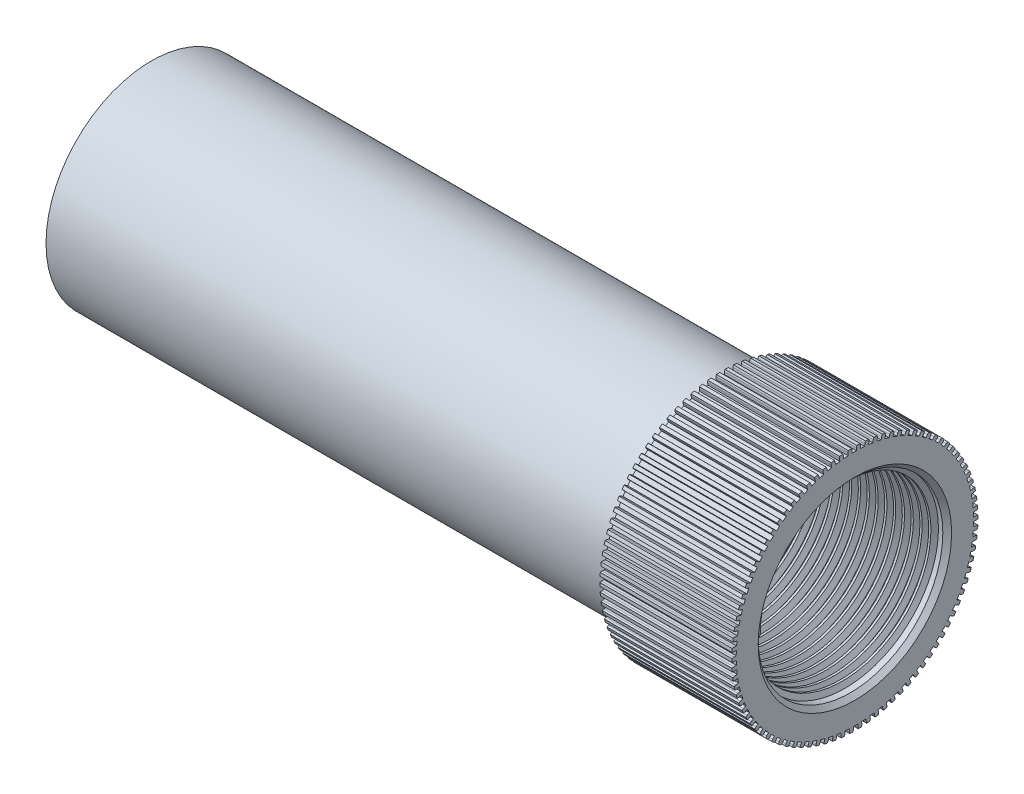
SolidWorks part; units mm, degrees
material "1060 Сплав"
ref_plane "Спереди" through (0, 0, 0) normal (0, 0, 1) x (1, 0, 0)
ref_plane "Сверху" through (0, 0, 0) normal (0, 1, 0) x (1, 0, 0)
ref_plane "Справа" through (0, 0, 0) normal (1, 0, 0) x (0, 0, -1)
sketch "Эскиз1" plane through (0, 0, 0) normal (0, 0, 1) x (1, 0, 0)
  line L0 (39.1314, 14) -> (24.1314, 14)
  line L1 (24.1314, 14) -> (24.1314, 12)
  line L2 (24.1314, 12) -> (-40.8686, 12)
  line L3 (-40.8686, 12) -> (-40.8686, 10.5)
  line L4 (-40.8686, 10.5) -> (-25.8686, 10.5)
  line L5 (-25.8686, 10.5) -> (-25.8686, 8.5)
  line L6 (-25.8686, 8.5) -> (23.1314, 8.5)
  line L7 (23.1314, 8.5) -> (23.1314, 10.5)
  line L8 (23.1314, 10.5) -> (39.1314, 10.5)
  line L9 (39.1314, 10.5) -> (39.1314, 14)
  line L10 (-1.2343, 0) -> (0, 0) construction
  line L11 (0, 0) -> (51.2914, 0) construction
  dimension "D1" = 12
  dimension "D2" = 65
  dimension "D3" = 2
  dimension "D4" = 15
  dimension "D5" = 10.5
  dimension "D6" = 3.5
  dimension "D7" = 8.5
  dimension "D8" = 10.5
  dimension "D9" = 16
  dimension "D10" = 15
revolve "Повернуть1" add sketch "Эскиз1" angle 360 about L11
chamfer "Фаска1" distance 0.5 angle 45 1 edges at (39.1314, 0, 10.5)
thread "Резьба1" pitch 1 method extrude profile "Профиль резьбы2" start angle 0, offset 0, length 15, pitch 1, diameter 21
ref_plane "Плоскость2" through (38.6314, 0, 10.5) normal (0, -1, 0) x (0, 0, 1)
sketch "Профиль резьбы2" plane through (38.6314, 0, 10.5) normal (0, -1, 0) x (0, 0, 1)
  line L0 (0, 0) -> (0, 1) construction
  line L11 (0, 0) -> (0, 0.875)
  line L12 (0, 0.875) -> (-0.5413, 0.5625)
  line L13 (-0.5413, 0.5625) -> (-0.5413, 0.3125)
  line L15 (-0.5413, 0.3125) -> (0, 0)
  line L17 (-0.5413, 0.4375) -> (0, 0.4375) construction
  point P2 (0, 0)
  dimension "Pitch" = 1
  dimension "Profile_Angle" = 60
  dimension "Profile_Land" = 0.25
  dimension "Profile_Height" = 0.5413
thread "Резьба2" pitch 1 method extrude profile "Профиль резьбы3" start angle 0, offset 0, length 15, pitch 1, diameter 21
ref_plane "Плоскость3" through (-40.8686, 0, -10.5) normal (0, -1, 0) x (0, 0, -1)
sketch "Профиль резьбы3" plane through (-40.8686, 0, -10.5) normal (0, -1, 0) x (0, 0, -1)
  line L0 (0, 0) -> (0, 1) construction
  line L11 (0, 0) -> (0, 0.875)
  line L12 (0, 0.875) -> (-0.5413, 0.5625)
  line L13 (-0.5413, 0.5625) -> (-0.5413, 0.3125)
  line L15 (-0.5413, 0.3125) -> (0, 0)
  line L17 (-0.5413, 0.4375) -> (0, 0.4375) construction
  point P2 (0, 0)
  dimension "Pitch" = 1
  dimension "Profile_Angle" = 60
  dimension "Profile_Land" = 0.25
  dimension "Profile_Height" = 0.5413
sketch "Эскиз2" plane through (39.1314, 0, 0) normal (1, 0, 0) x (0, 0, -1)
  line L0 (-0.0776, 1.5379) -> (-0.0776, 20.4101) construction
  line L1 (-0.3776, 14) -> (-0.3276, 13.8)
  line L2 (-0.3276, 13.8) -> (-0.3276, 13.5)
  line L3 (-0.3276, 13.5) -> (0.1724, 13.5)
  line L4 (0.1724, 13.5) -> (0.1724, 13.8)
  line L5 (0.1724, 13.8) -> (0.2224, 14)
  line L6 (0.2224, 14) -> (-0.3776, 14)
  line L7 (0.5999, 13.9922) -> (0.6358, 13.7892)
  line L8 (0.6358, 13.7892) -> (0.6149, 13.49)
  line L9 (0.6149, 13.49) -> (1.1137, 13.4551)
  line L10 (1.1137, 13.4551) -> (1.1346, 13.7544)
  line L11 (1.1346, 13.7544) -> (1.1984, 13.9504)
  line L12 (1.1984, 13.9504) -> (0.5999, 13.9922)
  line L13 (1.5745, 13.9163) -> (1.5961, 13.7113)
  line L14 (1.5961, 13.7113) -> (1.5544, 13.4142)
  line L15 (1.5544, 13.4142) -> (2.0495, 13.3446)
  line L16 (2.0495, 13.3446) -> (2.0913, 13.6417)
  line L17 (2.0913, 13.6417) -> (2.1686, 13.8328)
  line L18 (2.1686, 13.8328) -> (1.5745, 13.9163)
  line L19 (2.5414, 13.7726) -> (2.5487, 13.5666)
  line L20 (2.5487, 13.5666) -> (2.4863, 13.2731)
  line L21 (2.4863, 13.2731) -> (2.9754, 13.1692)
  line L22 (2.9754, 13.1692) -> (3.0378, 13.4626)
  line L23 (3.0378, 13.4626) -> (3.1283, 13.6478)
  line L24 (3.1283, 13.6478) -> (2.5414, 13.7726)
  line L25 (3.4959, 13.5618) -> (3.4888, 13.3557)
  line L26 (3.4888, 13.3557) -> (3.4062, 13.0673)
  line L27 (3.4062, 13.0673) -> (3.8868, 12.9295)
  line L28 (3.8868, 12.9295) -> (3.9695, 13.2179)
  line L29 (3.9695, 13.2179) -> (4.0727, 13.3964)
  line L30 (4.0727, 13.3964) -> (3.4959, 13.5618)
  line L31 (4.4334, 13.2849) -> (4.412, 13.0798)
  line L32 (4.412, 13.0798) -> (4.3094, 12.7979)
  line L33 (4.3094, 12.7979) -> (4.7792, 12.6269)
  line L34 (4.7792, 12.6269) -> (4.8818, 12.9088)
  line L35 (4.8818, 12.9088) -> (4.9972, 13.0796)
  line L36 (4.9972, 13.0796) -> (4.4334, 13.2849)
  line L37 (5.3493, 12.9432) -> (5.3136, 12.7402)
  line L38 (5.3136, 12.7402) -> (5.1916, 12.4661)
  line L39 (5.1916, 12.4661) -> (5.6484, 12.2628)
  line L40 (5.6484, 12.2628) -> (5.7704, 12.5368)
  line L41 (5.7704, 12.5368) -> (5.8974, 12.6992)
  line L42 (5.8974, 12.6992) -> (5.3493, 12.9432)
  line L43 (6.2392, 12.5386) -> (6.1894, 12.3385)
  line L44 (6.1894, 12.3385) -> (6.0486, 12.0736)
  line L45 (6.0486, 12.0736) -> (6.49, 11.8389)
  line L46 (6.49, 11.8389) -> (6.6309, 12.1038)
  line L47 (6.6309, 12.1038) -> (6.7689, 12.2569)
  line L48 (6.7689, 12.2569) -> (6.2392, 12.5386)
  line L49 (7.0986, 12.0728) -> (7.035, 11.8767)
  line L50 (7.035, 11.8767) -> (6.8761, 11.6223)
  line L51 (6.8761, 11.6223) -> (7.3001, 11.3573)
  line L52 (7.3001, 11.3573) -> (7.4591, 11.6117)
  line L53 (7.4591, 11.6117) -> (7.6074, 11.7548)
  line L54 (7.6074, 11.7548) -> (7.0986, 12.0728)
  line L55 (7.9235, 11.5482) -> (7.8464, 11.357)
  line L56 (7.8464, 11.357) -> (7.67, 11.1143)
  line L57 (7.67, 11.1143) -> (8.0745, 10.8204)
  line L58 (8.0745, 10.8204) -> (8.2509, 11.0631)
  line L59 (8.2509, 11.0631) -> (8.4089, 11.1955)
  line L60 (8.4089, 11.1955) -> (7.9235, 11.5482)
  line L61 (8.7097, 10.9674) -> (8.6195, 10.782)
  line L62 (8.6195, 10.782) -> (8.4266, 10.5522)
  line L63 (8.4266, 10.5522) -> (8.8097, 10.2308)
  line L64 (8.8097, 10.2308) -> (9.0025, 10.4606)
  line L65 (9.0025, 10.4606) -> (9.1694, 10.5817)
  line L66 (9.1694, 10.5817) -> (8.7097, 10.9674)
  line L67 (9.4536, 10.3331) -> (9.3506, 10.1545)
  line L68 (9.3506, 10.1545) -> (9.1422, 9.9387)
  line L69 (9.1422, 9.9387) -> (9.5019, 9.5914)
  line L70 (9.5019, 9.5914) -> (9.7103, 9.8072)
  line L71 (9.7103, 9.8072) -> (9.8852, 9.9163)
  line L72 (9.8852, 9.9163) -> (9.4536, 10.3331)
  line L73 (10.1513, 9.6485) -> (10.0362, 9.4775)
  line L74 (10.0362, 9.4775) -> (9.8132, 9.2767)
  line L75 (9.8132, 9.2767) -> (10.1478, 8.9052)
  line L76 (10.1478, 8.9052) -> (10.3707, 9.1059)
  line L77 (10.3707, 9.1059) -> (10.5528, 9.2026)
  line L78 (10.5528, 9.2026) -> (10.1513, 9.6485)
  line L79 (10.7997, 8.9168) -> (10.6728, 8.7543)
  line L80 (10.6728, 8.7543) -> (10.4364, 8.5696)
  line L81 (10.4364, 8.5696) -> (10.7443, 8.1756)
  line L82 (10.7443, 8.1756) -> (10.9807, 8.3603)
  line L83 (10.9807, 8.3603) -> (11.169, 8.444)
  line L84 (11.169, 8.444) -> (10.7997, 8.9168)
  line L85 (11.3954, 8.1418) -> (11.2575, 7.9885)
  line L86 (11.2575, 7.9885) -> (11.0088, 7.8207)
  line L87 (11.0088, 7.8207) -> (11.2884, 7.4062)
  line L88 (11.2884, 7.4062) -> (11.5371, 7.574)
  line L89 (11.5371, 7.574) -> (11.7309, 7.6444)
  line L90 (11.7309, 7.6444) -> (11.3954, 8.1418)
  line L91 (11.9355, 7.327) -> (11.7873, 7.1837)
  line L92 (11.7873, 7.1837) -> (11.5275, 7.0337)
  line L93 (11.5275, 7.0337) -> (11.7775, 6.6007)
  line L94 (11.7775, 6.6007) -> (12.0373, 6.7507)
  line L95 (12.0373, 6.7507) -> (12.2355, 6.8074)
  line L96 (12.2355, 6.8074) -> (11.9355, 7.327)
  line L97 (12.4176, 6.4766) -> (12.2597, 6.344)
  line L98 (12.2597, 6.344) -> (11.9901, 6.2125)
  line L99 (11.9901, 6.2125) -> (12.2093, 5.7631)
  line L100 (12.2093, 5.7631) -> (12.4789, 5.8946)
  line L101 (12.4789, 5.8946) -> (12.6806, 5.9373)
  line L102 (12.6806, 5.9373) -> (12.4176, 6.4766)
  line L103 (12.8391, 5.5946) -> (12.6724, 5.4734)
  line L104 (12.6724, 5.4734) -> (12.3942, 5.361)
  line L105 (12.3942, 5.361) -> (12.5815, 4.8974)
  line L106 (12.5815, 4.8974) -> (12.8597, 5.0098)
  line L107 (12.8597, 5.0098) -> (13.0639, 5.0383)
  line L108 (13.0639, 5.0383) -> (12.8391, 5.5946)
  line L109 (13.1981, 4.6854) -> (13.0233, 4.576)
  line L110 (13.0233, 4.576) -> (12.738, 4.4833)
  line L111 (12.738, 4.4833) -> (12.8925, 4.0078)
  line L112 (12.8925, 4.0078) -> (13.1778, 4.1005)
  line L113 (13.1778, 4.1005) -> (13.3835, 4.1148)
  line L114 (13.3835, 4.1148) -> (13.1981, 4.6854)
  line L115 (13.4928, 3.7533) -> (13.3108, 3.6564)
  line L116 (13.3108, 3.6564) -> (13.0197, 3.5839)
  line L117 (13.0197, 3.5839) -> (13.1407, 3.0987)
  line L118 (13.1407, 3.0987) -> (13.4318, 3.1713)
  line L119 (13.4318, 3.1713) -> (13.6379, 3.1712)
  line L120 (13.6379, 3.1712) -> (13.4928, 3.7533)
  line L121 (13.7217, 2.803) -> (13.5335, 2.719)
  line L122 (13.5335, 2.719) -> (13.238, 2.6669)
  line L123 (13.238, 2.6669) -> (13.3248, 2.1745)
  line L124 (13.3248, 2.1745) -> (13.6203, 2.2266)
  line L125 (13.6203, 2.2266) -> (13.8259, 2.2121)
  line L126 (13.8259, 2.2121) -> (13.7217, 2.803)
  line L127 (13.8838, 1.839) -> (13.6902, 1.7683)
  line L128 (13.6902, 1.7683) -> (13.3918, 1.737)
  line L129 (13.3918, 1.737) -> (13.4441, 1.2397)
  line L130 (13.4441, 1.2397) -> (13.7424, 1.2711)
  line L131 (13.7424, 1.2711) -> (13.9465, 1.2423)
  line L132 (13.9465, 1.2423) -> (13.8838, 1.839)
  line L133 (13.9783, 0.866) -> (13.7802, 0.8091)
  line L134 (13.7802, 0.8091) -> (13.4803, 0.7986)
  line L135 (13.4803, 0.7986) -> (13.4978, 0.2989)
  line L136 (13.4978, 0.2989) -> (13.7976, 0.3094)
  line L137 (13.7976, 0.3094) -> (13.9992, 0.2664)
  line L138 (13.9992, 0.2664) -> (13.9783, 0.866)
  line L139 (14.0047, -0.1112) -> (13.803, -0.1542)
  line L140 (13.803, -0.1542) -> (13.5032, -0.1437)
  line L141 (13.5032, -0.1437) -> (13.4858, -0.6434)
  line L142 (13.4858, -0.6434) -> (13.7856, -0.6539)
  line L143 (13.7856, -0.6539) -> (13.9837, -0.7108)
  line L144 (13.9837, -0.7108) -> (14.0047, -0.1112)
  line L145 (13.9628, -1.0878) -> (13.7587, -1.1166)
  line L146 (13.7587, -1.1166) -> (13.4603, -1.0853)
  line L147 (13.4603, -1.0853) -> (13.408, -1.5825)
  line L148 (13.408, -1.5825) -> (13.7064, -1.6139)
  line L149 (13.7064, -1.6139) -> (13.9001, -1.6845)
  line L150 (13.9001, -1.6845) -> (13.9628, -1.0878)
  line L151 (13.8529, -2.0592) -> (13.6472, -2.0737)
  line L152 (13.6472, -2.0737) -> (13.3518, -2.0216)
  line L153 (13.3518, -2.0216) -> (13.265, -2.514)
  line L154 (13.265, -2.514) -> (13.5604, -2.5661)
  line L155 (13.5604, -2.5661) -> (13.7487, -2.6501)
  line L156 (13.7487, -2.6501) -> (13.8529, -2.0592)
  line L157 (13.6755, -3.0205) -> (13.4693, -3.0206)
  line L158 (13.4693, -3.0206) -> (13.1783, -2.948)
  line L159 (13.1783, -2.948) -> (13.0573, -3.4332)
  line L160 (13.0573, -3.4332) -> (13.3484, -3.5058)
  line L161 (13.3484, -3.5058) -> (13.5303, -3.6027)
  line L162 (13.5303, -3.6027) -> (13.6755, -3.0205)
  line L163 (13.4315, -3.9671) -> (13.2258, -3.9528)
  line L164 (13.2258, -3.9528) -> (12.9405, -3.8601)
  line L165 (12.9405, -3.8601) -> (12.786, -4.3357)
  line L166 (12.786, -4.3357) -> (13.0713, -4.4284)
  line L167 (13.0713, -4.4284) -> (13.2461, -4.5377)
  line L168 (13.2461, -4.5377) -> (13.4315, -3.9671)
  line L169 (13.122, -4.8943) -> (12.9179, -4.8658)
  line L170 (12.9179, -4.8658) -> (12.6397, -4.7534)
  line L171 (12.6397, -4.7534) -> (12.4524, -5.217)
  line L172 (12.4524, -5.217) -> (12.7306, -5.3294)
  line L173 (12.7306, -5.3294) -> (12.8973, -5.4507)
  line L174 (12.8973, -5.4507) -> (13.122, -4.8943)
  line L175 (12.7487, -5.7978) -> (12.547, -5.755)
  line L176 (12.547, -5.755) -> (12.2773, -5.6235)
  line L177 (12.2773, -5.6235) -> (12.0582, -6.0729)
  line L178 (12.0582, -6.0729) -> (12.3278, -6.2044)
  line L179 (12.3278, -6.2044) -> (12.4856, -6.337)
  line L180 (12.4856, -6.337) -> (12.7487, -5.7978)
  line L181 (12.3132, -6.673) -> (12.115, -6.6163)
  line L182 (12.115, -6.6163) -> (11.8552, -6.4663)
  line L183 (11.8552, -6.4663) -> (11.6052, -6.8993)
  line L184 (11.6052, -6.8993) -> (11.865, -7.0493)
  line L185 (11.865, -7.0493) -> (12.0132, -7.1926)
  line L186 (12.0132, -7.1926) -> (12.3132, -6.673)
  line L187 (11.8177, -7.5156) -> (11.6239, -7.4452)
  line L188 (11.6239, -7.4452) -> (11.3752, -7.2775)
  line L189 (11.3752, -7.2775) -> (11.0956, -7.692)
  line L190 (11.0956, -7.692) -> (11.3443, -7.8598)
  line L191 (11.3443, -7.8598) -> (11.4822, -8.013)
  line L192 (11.4822, -8.013) -> (11.8177, -7.5156)
  line L193 (11.2647, -8.3217) -> (11.0763, -8.2379)
  line L194 (11.0763, -8.2379) -> (10.8399, -8.0532)
  line L195 (10.8399, -8.0532) -> (10.532, -8.4472)
  line L196 (10.532, -8.4472) -> (10.7684, -8.6319)
  line L197 (10.7684, -8.6319) -> (10.8953, -8.7945)
  line L198 (10.8953, -8.7945) -> (11.2647, -8.3217)
  line L199 (10.6567, -9.0872) -> (10.4746, -8.9905)
  line L200 (10.4746, -8.9905) -> (10.2517, -8.7898)
  line L201 (10.2517, -8.7898) -> (9.9171, -9.1613)
  line L202 (9.9171, -9.1613) -> (10.1401, -9.3621)
  line L203 (10.1401, -9.3621) -> (10.2552, -9.5331)
  line L204 (10.2552, -9.5331) -> (10.6567, -9.0872)
  line L205 (9.9969, -9.8084) -> (9.822, -9.6993)
  line L206 (9.822, -9.6993) -> (9.6136, -9.4835)
  line L207 (9.6136, -9.4835) -> (9.2539, -9.8308)
  line L208 (9.2539, -9.8308) -> (9.4623, -10.0466)
  line L209 (9.4623, -10.0466) -> (9.5653, -10.2252)
  line L210 (9.5653, -10.2252) -> (9.9969, -9.8084)
  line L211 (9.2883, -10.4819) -> (9.1215, -10.3608)
  line L212 (9.1215, -10.3608) -> (8.9286, -10.131)
  line L213 (8.9286, -10.131) -> (8.5456, -10.4524)
  line L214 (8.5456, -10.4524) -> (8.7384, -10.6822)
  line L215 (8.7384, -10.6822) -> (8.8287, -10.8676)
  line L216 (8.8287, -10.8676) -> (9.2883, -10.4819)
  line L217 (8.5345, -11.1043) -> (8.3765, -10.9719)
  line L218 (8.3765, -10.9719) -> (8.2002, -10.7291)
  line L219 (8.2002, -10.7291) -> (7.7957, -11.023)
  line L220 (7.7957, -11.023) -> (7.972, -11.2657)
  line L221 (7.972, -11.2657) -> (8.0491, -11.4569)
  line L222 (8.0491, -11.4569) -> (8.5345, -11.1043)
  line L223 (7.7391, -11.6726) -> (7.5907, -11.5294)
  line L224 (7.5907, -11.5294) -> (7.4318, -11.275)
  line L225 (7.4318, -11.275) -> (7.0077, -11.54)
  line L226 (7.0077, -11.54) -> (7.1667, -11.7944)
  line L227 (7.1667, -11.7944) -> (7.2303, -11.9905)
  line L228 (7.2303, -11.9905) -> (7.7391, -11.6726)
  line L229 (6.906, -12.184) -> (6.768, -12.0309)
  line L230 (6.768, -12.0309) -> (6.6272, -11.766)
  line L231 (6.6272, -11.766) -> (6.1857, -12.0007)
  line L232 (6.1857, -12.0007) -> (6.3265, -12.2656)
  line L233 (6.3265, -12.2656) -> (6.3763, -12.4657)
  line L234 (6.3763, -12.4657) -> (6.906, -12.184)
  line L235 (6.0393, -12.636) -> (5.9123, -12.4737)
  line L236 (5.9123, -12.4737) -> (5.7903, -12.1996)
  line L237 (5.7903, -12.1996) -> (5.3335, -12.403)
  line L238 (5.3335, -12.403) -> (5.4555, -12.677)
  line L239 (5.4555, -12.677) -> (5.4912, -12.8801)
  line L240 (5.4912, -12.8801) -> (6.0393, -12.636)
  line L241 (5.1431, -13.0265) -> (5.0278, -12.8557)
  line L242 (5.0278, -12.8557) -> (4.9252, -12.5738)
  line L243 (4.9252, -12.5738) -> (4.4553, -12.7448)
  line L244 (4.4553, -12.7448) -> (4.5579, -13.0267)
  line L245 (4.5579, -13.0267) -> (4.5793, -13.2317)
  line L246 (4.5793, -13.2317) -> (5.1431, -13.0265)
  line L247 (4.2219, -13.3536) -> (4.1187, -13.1751)
  line L248 (4.1187, -13.1751) -> (4.0361, -12.8867)
  line L249 (4.0361, -12.8867) -> (3.5554, -13.0245)
  line L250 (3.5554, -13.0245) -> (3.6381, -13.3129)
  line L251 (3.6381, -13.3129) -> (3.6452, -13.519)
  line L252 (3.6452, -13.519) -> (4.2219, -13.3536)
  line L253 (3.2802, -13.6156) -> (3.1897, -13.4303)
  line L254 (3.1897, -13.4303) -> (3.1273, -13.1369)
  line L255 (3.1273, -13.1369) -> (2.6382, -13.2408)
  line L256 (2.6382, -13.2408) -> (2.7006, -13.5343)
  line L257 (2.7006, -13.5343) -> (2.6933, -13.7403)
  line L258 (2.6933, -13.7403) -> (3.2802, -13.6156)
  line L259 (2.3224, -13.8112) -> (2.245, -13.6201)
  line L260 (2.245, -13.6201) -> (2.2033, -13.323)
  line L261 (2.2033, -13.323) -> (1.7082, -13.3926)
  line L262 (1.7082, -13.3926) -> (1.7499, -13.6897)
  line L263 (1.7499, -13.6897) -> (1.7282, -13.8947)
  line L264 (1.7282, -13.8947) -> (2.3224, -13.8112)
  line L265 (1.3533, -13.9396) -> (1.2895, -13.7435)
  line L266 (1.2895, -13.7435) -> (1.2686, -13.4443)
  line L267 (1.2686, -13.4443) -> (0.7698, -13.4791)
  line L268 (0.7698, -13.4791) -> (0.7907, -13.7784)
  line L269 (0.7907, -13.7784) -> (0.7548, -13.9814)
  line L270 (0.7548, -13.9814) -> (1.3533, -13.9396)
  line L271 (0.3776, -14) -> (0.3276, -13.8)
  line L272 (0.3276, -13.8) -> (0.3276, -13.5)
  line L273 (0.3276, -13.5) -> (-0.1724, -13.5)
  line L274 (-0.1724, -13.5) -> (-0.1724, -13.8)
  line L275 (-0.1724, -13.8) -> (-0.2224, -14)
  line L276 (-0.2224, -14) -> (0.3776, -14)
  line L277 (-0.5999, -13.9922) -> (-0.6358, -13.7892)
  line L278 (-0.6358, -13.7892) -> (-0.6149, -13.49)
  line L279 (-0.6149, -13.49) -> (-1.1137, -13.4551)
  line L280 (-1.1137, -13.4551) -> (-1.1346, -13.7544)
  line L281 (-1.1346, -13.7544) -> (-1.1984, -13.9504)
  line L282 (-1.1984, -13.9504) -> (-0.5999, -13.9922)
  line L283 (-1.5745, -13.9163) -> (-1.5961, -13.7113)
  line L284 (-1.5961, -13.7113) -> (-1.5544, -13.4142)
  line L285 (-1.5544, -13.4142) -> (-2.0495, -13.3446)
  line L286 (-2.0495, -13.3446) -> (-2.0913, -13.6417)
  line L287 (-2.0913, -13.6417) -> (-2.1686, -13.8328)
  line L288 (-2.1686, -13.8328) -> (-1.5745, -13.9163)
  line L289 (-2.5414, -13.7726) -> (-2.5487, -13.5666)
  line L290 (-2.5487, -13.5666) -> (-2.4863, -13.2731)
  line L291 (-2.4863, -13.2731) -> (-2.9754, -13.1692)
  line L292 (-2.9754, -13.1692) -> (-3.0378, -13.4626)
  line L293 (-3.0378, -13.4626) -> (-3.1283, -13.6478)
  line L294 (-3.1283, -13.6478) -> (-2.5414, -13.7726)
  line L295 (-3.4959, -13.5618) -> (-3.4888, -13.3557)
  line L296 (-3.4888, -13.3557) -> (-3.4062, -13.0673)
  line L297 (-3.4062, -13.0673) -> (-3.8868, -12.9295)
  line L298 (-3.8868, -12.9295) -> (-3.9695, -13.2179)
  line L299 (-3.9695, -13.2179) -> (-4.0727, -13.3964)
  line L300 (-4.0727, -13.3964) -> (-3.4959, -13.5618)
  line L301 (-4.4334, -13.2849) -> (-4.412, -13.0798)
  line L302 (-4.412, -13.0798) -> (-4.3094, -12.7979)
  line L303 (-4.3094, -12.7979) -> (-4.7792, -12.6269)
  line L304 (-4.7792, -12.6269) -> (-4.8818, -12.9088)
  line L305 (-4.8818, -12.9088) -> (-4.9972, -13.0796)
  line L306 (-4.9972, -13.0796) -> (-4.4334, -13.2849)
  line L307 (-5.3493, -12.9432) -> (-5.3136, -12.7402)
  line L308 (-5.3136, -12.7402) -> (-5.1916, -12.4661)
  line L309 (-5.1916, -12.4661) -> (-5.6484, -12.2628)
  line L310 (-5.6484, -12.2628) -> (-5.7704, -12.5368)
  line L311 (-5.7704, -12.5368) -> (-5.8974, -12.6992)
  line L312 (-5.8974, -12.6992) -> (-5.3493, -12.9432)
  line L313 (-6.2392, -12.5386) -> (-6.1894, -12.3385)
  line L314 (-6.1894, -12.3385) -> (-6.0486, -12.0736)
  line L315 (-6.0486, -12.0736) -> (-6.49, -11.8389)
  line L316 (-6.49, -11.8389) -> (-6.6309, -12.1038)
  line L317 (-6.6309, -12.1038) -> (-6.7689, -12.2569)
  line L318 (-6.7689, -12.2569) -> (-6.2392, -12.5386)
  line L319 (-7.0986, -12.0728) -> (-7.035, -11.8767)
  line L320 (-7.035, -11.8767) -> (-6.8761, -11.6223)
  line L321 (-6.8761, -11.6223) -> (-7.3001, -11.3573)
  line L322 (-7.3001, -11.3573) -> (-7.4591, -11.6117)
  line L323 (-7.4591, -11.6117) -> (-7.6074, -11.7548)
  line L324 (-7.6074, -11.7548) -> (-7.0986, -12.0728)
  line L325 (-7.9235, -11.5482) -> (-7.8464, -11.357)
  line L326 (-7.8464, -11.357) -> (-7.67, -11.1143)
  line L327 (-7.67, -11.1143) -> (-8.0745, -10.8204)
  line L328 (-8.0745, -10.8204) -> (-8.2509, -11.0631)
  line L329 (-8.2509, -11.0631) -> (-8.4089, -11.1955)
  line L330 (-8.4089, -11.1955) -> (-7.9235, -11.5482)
  line L331 (-8.7097, -10.9674) -> (-8.6195, -10.782)
  line L332 (-8.6195, -10.782) -> (-8.4266, -10.5522)
  line L333 (-8.4266, -10.5522) -> (-8.8097, -10.2308)
  line L334 (-8.8097, -10.2308) -> (-9.0025, -10.4606)
  line L335 (-9.0025, -10.4606) -> (-9.1694, -10.5817)
  line L336 (-9.1694, -10.5817) -> (-8.7097, -10.9674)
  line L337 (-9.4536, -10.3331) -> (-9.3506, -10.1545)
  line L338 (-9.3506, -10.1545) -> (-9.1422, -9.9387)
  line L339 (-9.1422, -9.9387) -> (-9.5019, -9.5914)
  line L340 (-9.5019, -9.5914) -> (-9.7103, -9.8072)
  line L341 (-9.7103, -9.8072) -> (-9.8852, -9.9163)
  line L342 (-9.8852, -9.9163) -> (-9.4536, -10.3331)
  line L343 (-10.1513, -9.6485) -> (-10.0362, -9.4775)
  line L344 (-10.0362, -9.4775) -> (-9.8132, -9.2767)
  line L345 (-9.8132, -9.2767) -> (-10.1478, -8.9052)
  line L346 (-10.1478, -8.9052) -> (-10.3707, -9.1059)
  line L347 (-10.3707, -9.1059) -> (-10.5528, -9.2026)
  line L348 (-10.5528, -9.2026) -> (-10.1513, -9.6485)
  line L349 (-10.7997, -8.9168) -> (-10.6728, -8.7543)
  line L350 (-10.6728, -8.7543) -> (-10.4364, -8.5696)
  line L351 (-10.4364, -8.5696) -> (-10.7443, -8.1756)
  line L352 (-10.7443, -8.1756) -> (-10.9807, -8.3603)
  line L353 (-10.9807, -8.3603) -> (-11.169, -8.444)
  line L354 (-11.169, -8.444) -> (-10.7997, -8.9168)
  line L355 (-11.3954, -8.1418) -> (-11.2575, -7.9885)
  line L356 (-11.2575, -7.9885) -> (-11.0088, -7.8207)
  line L357 (-11.0088, -7.8207) -> (-11.2884, -7.4062)
  line L358 (-11.2884, -7.4062) -> (-11.5371, -7.574)
  line L359 (-11.5371, -7.574) -> (-11.7309, -7.6444)
  line L360 (-11.7309, -7.6444) -> (-11.3954, -8.1418)
  line L361 (-11.9355, -7.327) -> (-11.7873, -7.1837)
  line L362 (-11.7873, -7.1837) -> (-11.5275, -7.0337)
  line L363 (-11.5275, -7.0337) -> (-11.7775, -6.6007)
  line L364 (-11.7775, -6.6007) -> (-12.0373, -6.7507)
  line L365 (-12.0373, -6.7507) -> (-12.2355, -6.8074)
  line L366 (-12.2355, -6.8074) -> (-11.9355, -7.327)
  line L367 (-12.4176, -6.4766) -> (-12.2597, -6.344)
  line L368 (-12.2597, -6.344) -> (-11.9901, -6.2125)
  line L369 (-11.9901, -6.2125) -> (-12.2093, -5.7631)
  line L370 (-12.2093, -5.7631) -> (-12.4789, -5.8946)
  line L371 (-12.4789, -5.8946) -> (-12.6806, -5.9373)
  line L372 (-12.6806, -5.9373) -> (-12.4176, -6.4766)
  line L373 (-12.8391, -5.5946) -> (-12.6724, -5.4734)
  line L374 (-12.6724, -5.4734) -> (-12.3942, -5.361)
  line L375 (-12.3942, -5.361) -> (-12.5815, -4.8974)
  line L376 (-12.5815, -4.8974) -> (-12.8597, -5.0098)
  line L377 (-12.8597, -5.0098) -> (-13.0639, -5.0383)
  line L378 (-13.0639, -5.0383) -> (-12.8391, -5.5946)
  line L379 (-13.1981, -4.6854) -> (-13.0233, -4.576)
  line L380 (-13.0233, -4.576) -> (-12.738, -4.4833)
  line L381 (-12.738, -4.4833) -> (-12.8925, -4.0078)
  line L382 (-12.8925, -4.0078) -> (-13.1778, -4.1005)
  line L383 (-13.1778, -4.1005) -> (-13.3835, -4.1148)
  line L384 (-13.3835, -4.1148) -> (-13.1981, -4.6854)
  line L385 (-13.4928, -3.7533) -> (-13.3108, -3.6564)
  line L386 (-13.3108, -3.6564) -> (-13.0197, -3.5839)
  line L387 (-13.0197, -3.5839) -> (-13.1407, -3.0987)
  line L388 (-13.1407, -3.0987) -> (-13.4318, -3.1713)
  line L389 (-13.4318, -3.1713) -> (-13.6379, -3.1712)
  line L390 (-13.6379, -3.1712) -> (-13.4928, -3.7533)
  line L391 (-13.7217, -2.803) -> (-13.5335, -2.719)
  line L392 (-13.5335, -2.719) -> (-13.238, -2.6669)
  line L393 (-13.238, -2.6669) -> (-13.3248, -2.1745)
  line L394 (-13.3248, -2.1745) -> (-13.6203, -2.2266)
  line L395 (-13.6203, -2.2266) -> (-13.8259, -2.2121)
  line L396 (-13.8259, -2.2121) -> (-13.7217, -2.803)
  line L397 (-13.8838, -1.839) -> (-13.6902, -1.7683)
  line L398 (-13.6902, -1.7683) -> (-13.3918, -1.737)
  line L399 (-13.3918, -1.737) -> (-13.4441, -1.2397)
  line L400 (-13.4441, -1.2397) -> (-13.7424, -1.2711)
  line L401 (-13.7424, -1.2711) -> (-13.9465, -1.2423)
  line L402 (-13.9465, -1.2423) -> (-13.8838, -1.839)
  line L403 (-13.9783, -0.866) -> (-13.7802, -0.8091)
  line L404 (-13.7802, -0.8091) -> (-13.4803, -0.7986)
  line L405 (-13.4803, -0.7986) -> (-13.4978, -0.2989)
  line L406 (-13.4978, -0.2989) -> (-13.7976, -0.3094)
  line L407 (-13.7976, -0.3094) -> (-13.9992, -0.2664)
  line L408 (-13.9992, -0.2664) -> (-13.9783, -0.866)
  line L409 (-14.0047, 0.1112) -> (-13.803, 0.1542)
  line L410 (-13.803, 0.1542) -> (-13.5032, 0.1437)
  line L411 (-13.5032, 0.1437) -> (-13.4858, 0.6434)
  line L412 (-13.4858, 0.6434) -> (-13.7856, 0.6539)
  line L413 (-13.7856, 0.6539) -> (-13.9837, 0.7108)
  line L414 (-13.9837, 0.7108) -> (-14.0047, 0.1112)
  line L415 (-13.9628, 1.0878) -> (-13.7587, 1.1166)
  line L416 (-13.7587, 1.1166) -> (-13.4603, 1.0853)
  line L417 (-13.4603, 1.0853) -> (-13.408, 1.5825)
  line L418 (-13.408, 1.5825) -> (-13.7064, 1.6139)
  line L419 (-13.7064, 1.6139) -> (-13.9001, 1.6845)
  line L420 (-13.9001, 1.6845) -> (-13.9628, 1.0878)
  line L421 (-13.8529, 2.0592) -> (-13.6472, 2.0737)
  line L422 (-13.6472, 2.0737) -> (-13.3518, 2.0216)
  line L423 (-13.3518, 2.0216) -> (-13.265, 2.514)
  line L424 (-13.265, 2.514) -> (-13.5604, 2.5661)
  line L425 (-13.5604, 2.5661) -> (-13.7487, 2.6501)
  line L426 (-13.7487, 2.6501) -> (-13.8529, 2.0592)
  line L427 (-13.6755, 3.0205) -> (-13.4693, 3.0206)
  line L428 (-13.4693, 3.0206) -> (-13.1783, 2.948)
  line L429 (-13.1783, 2.948) -> (-13.0573, 3.4332)
  line L430 (-13.0573, 3.4332) -> (-13.3484, 3.5058)
  line L431 (-13.3484, 3.5058) -> (-13.5303, 3.6027)
  line L432 (-13.5303, 3.6027) -> (-13.6755, 3.0205)
  line L433 (-13.4315, 3.9671) -> (-13.2258, 3.9528)
  line L434 (-13.2258, 3.9528) -> (-12.9405, 3.8601)
  line L435 (-12.9405, 3.8601) -> (-12.786, 4.3357)
  line L436 (-12.786, 4.3357) -> (-13.0713, 4.4284)
  line L437 (-13.0713, 4.4284) -> (-13.2461, 4.5377)
  line L438 (-13.2461, 4.5377) -> (-13.4315, 3.9671)
  line L439 (-13.122, 4.8943) -> (-12.9179, 4.8658)
  line L440 (-12.9179, 4.8658) -> (-12.6397, 4.7534)
  line L441 (-12.6397, 4.7534) -> (-12.4524, 5.217)
  line L442 (-12.4524, 5.217) -> (-12.7306, 5.3294)
  line L443 (-12.7306, 5.3294) -> (-12.8973, 5.4507)
  line L444 (-12.8973, 5.4507) -> (-13.122, 4.8943)
  line L445 (-12.7487, 5.7978) -> (-12.547, 5.755)
  line L446 (-12.547, 5.755) -> (-12.2773, 5.6235)
  line L447 (-12.2773, 5.6235) -> (-12.0582, 6.0729)
  line L448 (-12.0582, 6.0729) -> (-12.3278, 6.2044)
  line L449 (-12.3278, 6.2044) -> (-12.4856, 6.337)
  line L450 (-12.4856, 6.337) -> (-12.7487, 5.7978)
  line L451 (-12.3132, 6.673) -> (-12.115, 6.6163)
  line L452 (-12.115, 6.6163) -> (-11.8552, 6.4663)
  line L453 (-11.8552, 6.4663) -> (-11.6052, 6.8993)
  line L454 (-11.6052, 6.8993) -> (-11.865, 7.0493)
  line L455 (-11.865, 7.0493) -> (-12.0132, 7.1926)
  line L456 (-12.0132, 7.1926) -> (-12.3132, 6.673)
  line L457 (-11.8177, 7.5156) -> (-11.6239, 7.4452)
  line L458 (-11.6239, 7.4452) -> (-11.3752, 7.2775)
  line L459 (-11.3752, 7.2775) -> (-11.0956, 7.692)
  line L460 (-11.0956, 7.692) -> (-11.3443, 7.8598)
  line L461 (-11.3443, 7.8598) -> (-11.4822, 8.013)
  line L462 (-11.4822, 8.013) -> (-11.8177, 7.5156)
  line L463 (-11.2647, 8.3217) -> (-11.0763, 8.2379)
  line L464 (-11.0763, 8.2379) -> (-10.8399, 8.0532)
  line L465 (-10.8399, 8.0532) -> (-10.532, 8.4472)
  line L466 (-10.532, 8.4472) -> (-10.7684, 8.6319)
  line L467 (-10.7684, 8.6319) -> (-10.8953, 8.7945)
  line L468 (-10.8953, 8.7945) -> (-11.2647, 8.3217)
  line L469 (-10.6567, 9.0872) -> (-10.4746, 8.9905)
  line L470 (-10.4746, 8.9905) -> (-10.2517, 8.7898)
  line L471 (-10.2517, 8.7898) -> (-9.9171, 9.1613)
  line L472 (-9.9171, 9.1613) -> (-10.1401, 9.3621)
  line L473 (-10.1401, 9.3621) -> (-10.2552, 9.5331)
  line L474 (-10.2552, 9.5331) -> (-10.6567, 9.0872)
  line L475 (-9.9969, 9.8084) -> (-9.822, 9.6993)
  line L476 (-9.822, 9.6993) -> (-9.6136, 9.4835)
  line L477 (-9.6136, 9.4835) -> (-9.2539, 9.8308)
  line L478 (-9.2539, 9.8308) -> (-9.4623, 10.0466)
  line L479 (-9.4623, 10.0466) -> (-9.5653, 10.2252)
  line L480 (-9.5653, 10.2252) -> (-9.9969, 9.8084)
  line L481 (-9.2883, 10.4819) -> (-9.1215, 10.3608)
  line L482 (-9.1215, 10.3608) -> (-8.9286, 10.131)
  line L483 (-8.9286, 10.131) -> (-8.5456, 10.4524)
  line L484 (-8.5456, 10.4524) -> (-8.7384, 10.6822)
  line L485 (-8.7384, 10.6822) -> (-8.8287, 10.8676)
  line L486 (-8.8287, 10.8676) -> (-9.2883, 10.4819)
  line L487 (-8.5345, 11.1043) -> (-8.3765, 10.9719)
  line L488 (-8.3765, 10.9719) -> (-8.2002, 10.7291)
  line L489 (-8.2002, 10.7291) -> (-7.7957, 11.023)
  line L490 (-7.7957, 11.023) -> (-7.972, 11.2657)
  line L491 (-7.972, 11.2657) -> (-8.0491, 11.4569)
  line L492 (-8.0491, 11.4569) -> (-8.5345, 11.1043)
  line L493 (-7.7391, 11.6726) -> (-7.5907, 11.5294)
  line L494 (-7.5907, 11.5294) -> (-7.4318, 11.275)
  line L495 (-7.4318, 11.275) -> (-7.0077, 11.54)
  line L496 (-7.0077, 11.54) -> (-7.1667, 11.7944)
  line L497 (-7.1667, 11.7944) -> (-7.2303, 11.9905)
  line L498 (-7.2303, 11.9905) -> (-7.7391, 11.6726)
  line L499 (-6.906, 12.184) -> (-6.768, 12.0309)
  line L500 (-6.768, 12.0309) -> (-6.6272, 11.766)
  line L501 (-6.6272, 11.766) -> (-6.1857, 12.0007)
  line L502 (-6.1857, 12.0007) -> (-6.3265, 12.2656)
  line L503 (-6.3265, 12.2656) -> (-6.3763, 12.4657)
  line L504 (-6.3763, 12.4657) -> (-6.906, 12.184)
  line L505 (-6.0393, 12.636) -> (-5.9123, 12.4737)
  line L506 (-5.9123, 12.4737) -> (-5.7903, 12.1996)
  line L507 (-5.7903, 12.1996) -> (-5.3335, 12.403)
  line L508 (-5.3335, 12.403) -> (-5.4555, 12.677)
  line L509 (-5.4555, 12.677) -> (-5.4912, 12.8801)
  line L510 (-5.4912, 12.8801) -> (-6.0393, 12.636)
  line L511 (-5.1431, 13.0265) -> (-5.0278, 12.8557)
  line L512 (-5.0278, 12.8557) -> (-4.9252, 12.5738)
  line L513 (-4.9252, 12.5738) -> (-4.4553, 12.7448)
  line L514 (-4.4553, 12.7448) -> (-4.5579, 13.0267)
  line L515 (-4.5579, 13.0267) -> (-4.5793, 13.2317)
  line L516 (-4.5793, 13.2317) -> (-5.1431, 13.0265)
  line L517 (-4.2219, 13.3536) -> (-4.1187, 13.1751)
  line L518 (-4.1187, 13.1751) -> (-4.0361, 12.8867)
  line L519 (-4.0361, 12.8867) -> (-3.5554, 13.0245)
  line L520 (-3.5554, 13.0245) -> (-3.6381, 13.3129)
  line L521 (-3.6381, 13.3129) -> (-3.6452, 13.519)
  line L522 (-3.6452, 13.519) -> (-4.2219, 13.3536)
  line L523 (-3.2802, 13.6156) -> (-3.1897, 13.4303)
  line L524 (-3.1897, 13.4303) -> (-3.1273, 13.1369)
  line L525 (-3.1273, 13.1369) -> (-2.6382, 13.2408)
  line L526 (-2.6382, 13.2408) -> (-2.7006, 13.5343)
  line L527 (-2.7006, 13.5343) -> (-2.6933, 13.7403)
  line L528 (-2.6933, 13.7403) -> (-3.2802, 13.6156)
  line L529 (-2.3224, 13.8112) -> (-2.245, 13.6201)
  line L530 (-2.245, 13.6201) -> (-2.2033, 13.323)
  line L531 (-2.2033, 13.323) -> (-1.7082, 13.3926)
  line L532 (-1.7082, 13.3926) -> (-1.7499, 13.6897)
  line L533 (-1.7499, 13.6897) -> (-1.7282, 13.8947)
  line L534 (-1.7282, 13.8947) -> (-2.3224, 13.8112)
  line L535 (-1.3533, 13.9396) -> (-1.2895, 13.7435)
  line L536 (-1.2895, 13.7435) -> (-1.2686, 13.4443)
  line L537 (-1.2686, 13.4443) -> (-0.7698, 13.4791)
  line L538 (-0.7698, 13.4791) -> (-0.7907, 13.7784)
  line L539 (-0.7907, 13.7784) -> (-0.7548, 13.9814)
  line L540 (-0.7548, 13.9814) -> (-1.3533, 13.9396)
  circle A0 centre (0, 0) radius 14 construction
  point P546 (0, 0)
  dimension "D1" = 0.5
  dimension "D2" = 0.25
  dimension "D3" = 0.3
  dimension "D4" = 0.2
  dimension "D5" = 0.6
  dimension "D6" = 13.5
  dimension "D7" = 90
extrude "Вырез-Вытянуть1" cut sketch "Эскиз2" against normal up to next (15 mm away)
